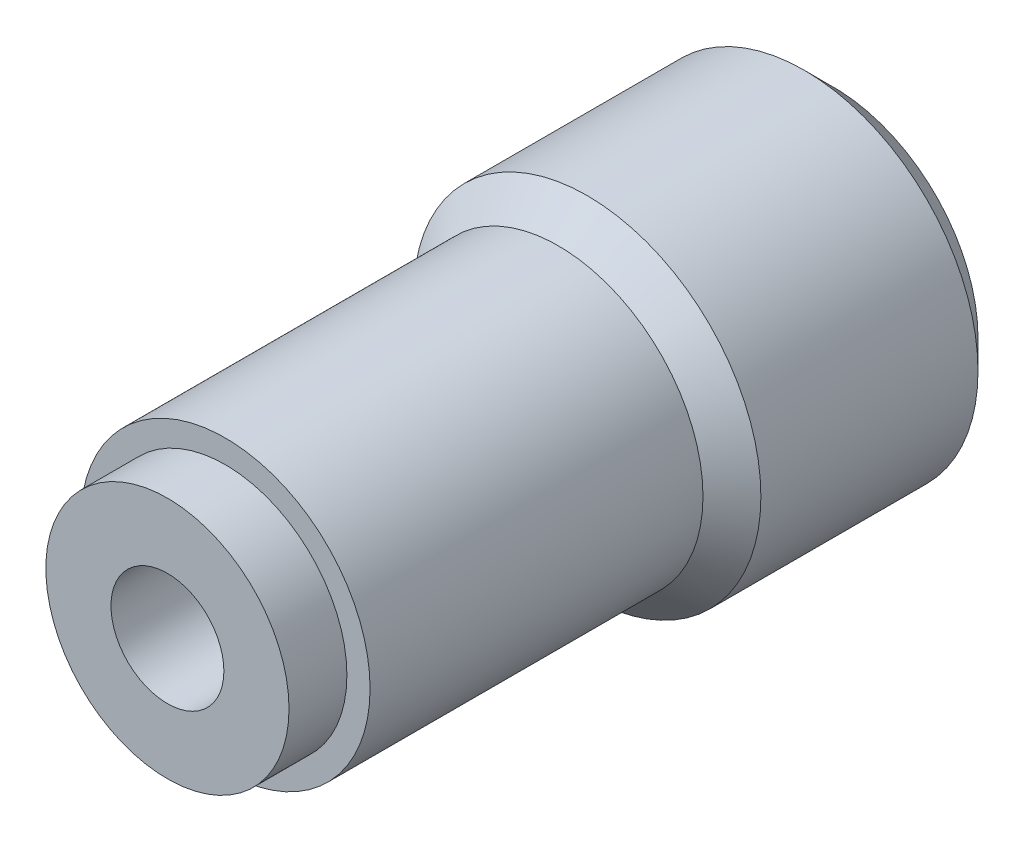
SolidWorks part; units mm, degrees
ref_plane "정면" through (0, 0, 0) normal (0, 0, 1) x (1, 0, 0)
ref_plane "윗면" through (0, 0, 0) normal (0, 1, 0) x (1, 0, 0)
ref_plane "우측면" through (0, 0, 0) normal (1, 0, 0) x (0, 0, -1)
sketch "스케치1" plane through (0, 0, 0) normal (0, 0, 1) x (1, 0, 0)
  circle A0 centre (0, 0) radius 5
  circle A1 centre (0, 0) radius 1.95
  dimension "D1" = 10
  dimension "D2" = 3.9
extrude "보스-돌출1" add sketch "스케치1" along normal blind 15
sketch "스케치3" plane through (0, 0, 0) normal (0, 0, 1) x (1, 0, 0)
  circle A0 centre (0, 0) radius 3.5
  dimension "D1" = 7
extrude "컷-돌출1" cut sketch "스케치3" along normal blind 4
sketch "스케치4" plane through (0, 0, 0) normal (0, 0, 1) x (1, 0, 0)
  circle A0 centre (0, 0) radius 6
  circle A1 centre (0, 0) radius 3.5
  dimension "D1" = 7
  dimension "D2" = 12
extrude "보스-돌출2" add sketch "스케치4" against normal blind 8
chamfer "모따기1" distance 1.5 angle 45 1 edges at (5, 0, 0)
chamfer "모따기2" distance 1 angle 45 1 edges at (6, 0, -8)
sketch "스케치9" plane through (0, 0, 15) normal (0, 0, 1) x (1, 0, 0)
  circle A0 centre (0, 0) radius 4.2
  circle A1 centre (0, 0) radius 5
  dimension "D1" = 10
  dimension "D2" = 8.4
extrude "컷-돌출4" cut sketch "스케치9" against normal blind 2
